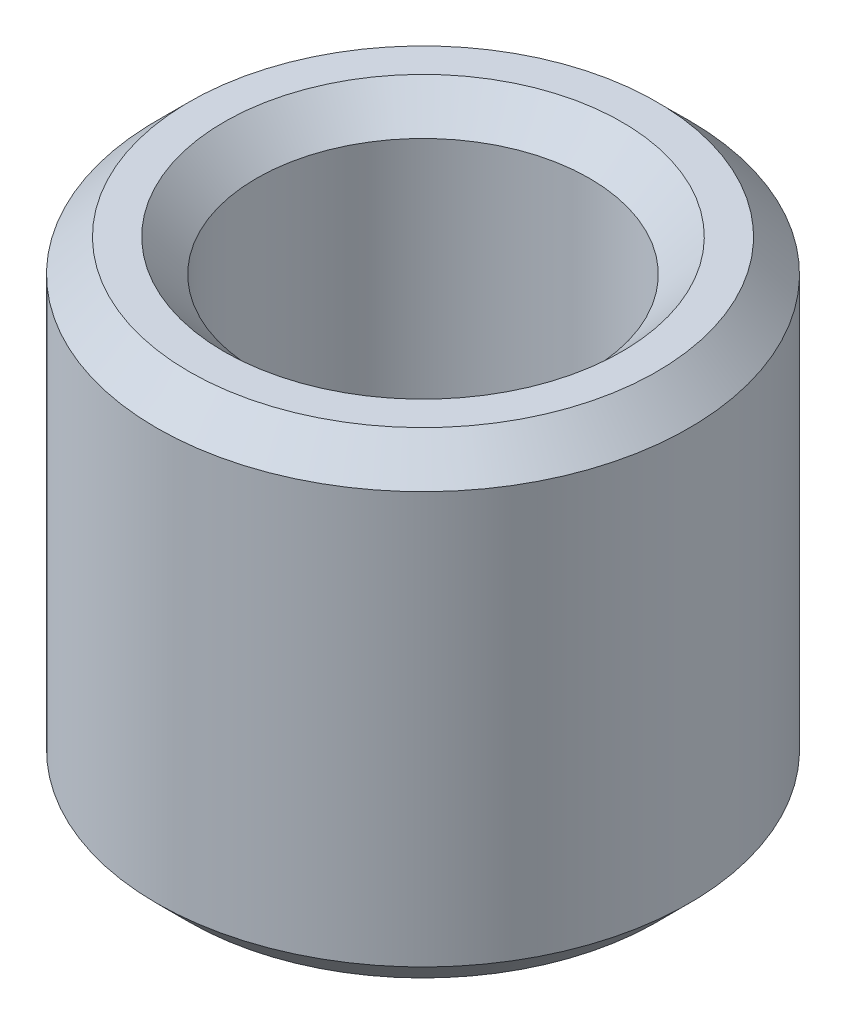
SolidWorks part; units mm, degrees
ref_plane "Front Plane" through (0, 0, 0) normal (0, 0, 1) x (1, 0, 0)
ref_plane "Top Plane" through (0, 0, 0) normal (0, 1, 0) x (1, 0, 0)
ref_plane "Right Plane" through (0, 0, 0) normal (1, 0, 0) x (0, 0, -1)
sketch "Sketch1" plane through (0, 0, 0) normal (0, 1, 0) x (1, 0, 0)
  circle A0 centre (0, 0) radius 22.5
  dimension "SLEEVE_OD" = 45
extrude "Boss-Extrude1" add sketch "Sketch1" along normal blind 40.2783
sketch "Sketch2" plane through (0, 0, 0) normal (0, 1, 0) x (1, 0, 0)
  circle A0 centre (0, 0) radius 14.0629
  dimension "BORE_D" = 28.1259
extrude "Cut-Extrude1" cut sketch "Sketch2" along normal through all
chamfer "Chamfer1" distance 2.7466 angle 45 4 edges at (0, 40.2783, 14.0629) (0, 0, 14.0629) (0, 0, 22.5) (0, 40.2783, 22.5)
